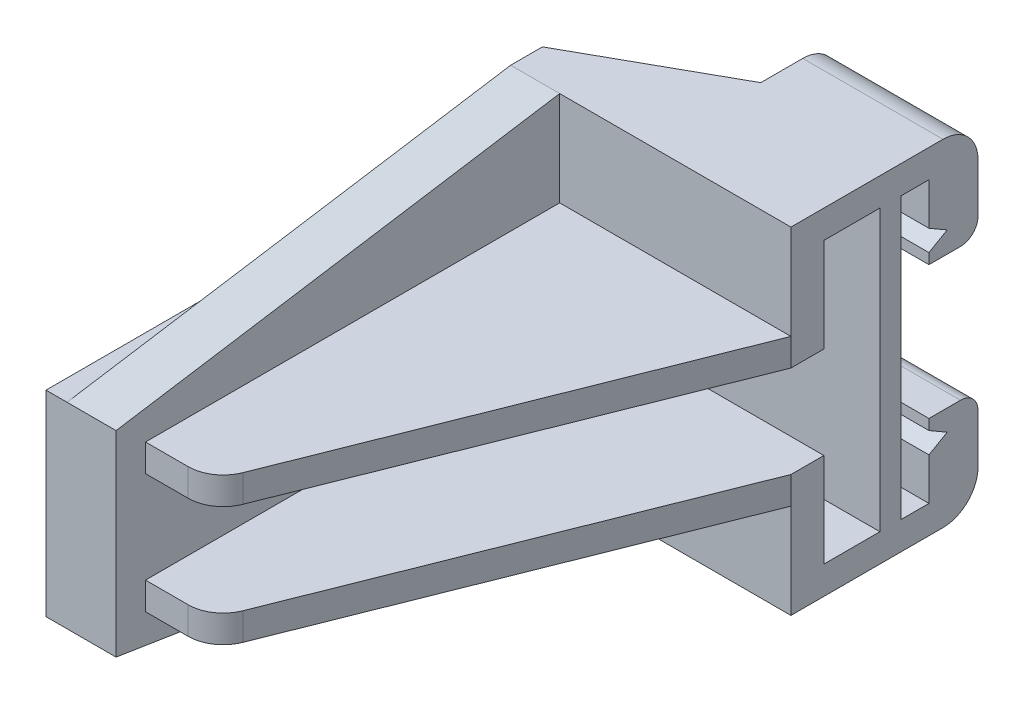
SolidWorks part; units mm, degrees
ref_plane "정면" through (0, 0, 0) normal (0, 0, 1) x (1, 0, 0)
ref_plane "윗면" through (0, 0, 0) normal (0, 1, 0) x (1, 0, 0)
ref_plane "우측면" through (0, 0, 0) normal (1, 0, 0) x (0, 0, -1)
sketch "스케치1" plane through (0, 0, 0) normal (1, 0, 0) x (0, 0, -1)
  line L1 (0, 0) -> (90, 0)
  line L2 (0, 0) -> (0, 48)
  line L3 (0, 48) -> (90, 48)
  line L4 (90, 0) -> (90, 48)
  dimension "D1" = 48
  dimension "D2" = 90
extrude "보스-돌출1" add sketch "스케치1" along normal blind 40
sketch "스케치2" plane through (40, 0, 0) normal (1, 0, 0) x (0, 0, -1)
  line L0 (90, 48) -> (0, 48) construction
  line L1 (79, 44) -> (83, 44)
  line L2 (79, 44) -> (79, 4)
  line L3 (79, 4) -> (83, 4)
  line L4 (83, 44) -> (83, 38)
  line L5 (0, 0) -> (90, 0) construction
  line L6 (90, 0) -> (90, 48) construction
  line L7 (83, 38) -> (85.5981, 36.5)
  line L8 (85.5981, 36.5) -> (83, 35)
  line L9 (-9.108, 24) -> (98.6493, 24) construction
  line L10 (85.5981, 11.5) -> (83, 13)
  line L11 (83, 10) -> (85.5981, 11.5)
  line L12 (83, 35) -> (83, 33.5)
  line L13 (83, 10) -> (83, 4)
  line L14 (83, 14.5) -> (83, 13)
  line L15 (83, 33.5) -> (90, 33.5)
  line L17 (83, 14.5) -> (90, 14.5)
  line L18 (90, 33.5) -> (90, 14.5)
  line L19 (0, 38) -> (63.304, 48)
  line L20 (0, 48) -> (0, 0) construction
  line L21 (63.304, 48) -> (0, 48)
  line L22 (0, 48) -> (0, 38)
  line L23 (0, 10) -> (63.304, 0)
  line L24 (63.304, 0) -> (0, 0)
  line L25 (0, 0) -> (0, 10)
  dimension "D1" = 4
  dimension "D2" = 4
  dimension "D3" = 4
  dimension "D4" = 7
  dimension "D5" = 60
  dimension "D6" = 3
  dimension "D7" = 60
  dimension "D8" = 14.5
  dimension "D9" = 6
  dimension "D10" = 14.5
extrude "컷-돌출1" cut sketch "스케치2" against normal blind 40
sketch "스케치3" plane through (0, 48, 0) normal (0, 1, 0) x (1, 0, 0)
  line L0 (0, 67.8468) -> (20, 79)
  line L1 (0, 90) -> (0, 63.304) construction
  line L2 (20, 79) -> (20, 90)
  line L3 (40, 90) -> (0, 90) construction
  line L4 (20, 90) -> (0, 90)
  line L5 (0, 90) -> (0, 67.8468)
extrude "컷-돌출2" cut sketch "스케치3" against normal through all
sketch "스케치4" plane through (0, 48, 0) normal (0, 1, 0) x (1, 0, 0)
  line L0 (40, 63.304) -> (14.8076, 0)
  line L1 (0, 0) -> (40, 0) construction
  line L2 (14.8076, 0) -> (40, 0)
  line L3 (40, 0) -> (40, 63.304)
extrude "컷-돌출3" cut sketch "스케치4" against normal through all
sketch "스케치5" plane through (40, 0, 0) normal (1, 0, 0) x (0, 0, -1)
  line L0 (-7.1778, 24) -> (95.0444, 24) construction
  line L1 (63.304, 0) -> (63.304, 48) construction
  line L2 (4.2, 34.4889) -> (63.304, 34.4889)
  line L3 (4.2, 34.4889) -> (4.2, 30.5778)
  line L4 (4.2, 30.5778) -> (63.304, 30.5778)
  line L6 (4.2, 17.4222) -> (63.304, 17.4222)
  line L8 (4.2, 13.5111) -> (63.304, 13.5111)
  line L9 (4.2, 13.5111) -> (4.2, 17.4222)
  line L10 (63.304, 34.4889) -> (63.304, 48)
  line L11 (63.304, 48) -> (0, 38)
  line L12 (0, 38) -> (0, 10)
  line L13 (0, 10) -> (63.304, 0)
  line L14 (63.304, 0) -> (63.304, 13.5111)
  line L15 (63.304, 30.5778) -> (63.304, 17.4222)
extrude "컷-돌출4" cut sketch "스케치5" against normal blind 33
sketch "스케치6" plane through (40, 0, 0) normal (1, 0, 0) x (0, 0, -1)
  line L0 (79, 44) -> (79, 4) construction
  line L1 (76, 44) -> (68, 44)
  line L2 (76, 44) -> (76, 4)
  line L3 (76, 4) -> (68, 4)
  line L4 (68, 44) -> (68, 4)
  dimension "D1" = 3
  dimension "D2" = 8
extrude "컷-돌출5" cut sketch "스케치6" against normal through all
sketch "스케치7" plane through (0, 0, -63.304) normal (0, 0, 1) x (1, 0, 0)
  line L0 (7, 30.5778) -> (40, 30.5778) construction
  line L1 (20, 30.5778) -> (40, 30.5778)
  line L2 (20, 30.5778) -> (20, 17.4222)
  line L3 (20, 17.4222) -> (40, 17.4222)
  line L4 (40, 30.5778) -> (40, 17.4222)
extrude "컷-돌출6" cut sketch "스케치7" against normal blind 5
sketch "스케치8" plane through (0, 0, 0) normal (-1, 0, 0) x (0, 0, 1)
  line L1 (0, 38) -> (-28.2, 38)
  line L2 (0, 38) -> (0, 10)
  line L3 (0, 10) -> (-28.2, 10)
  line L4 (-28.2, 38) -> (-28.2, 10)
extrude "보스-돌출2" add sketch "스케치8" along normal blind 3
sketch "스케치9" plane through (0, 0, -79) normal (0, 0, -1) x (-1, 0, 0)
  circle A0 centre (-30, 24) radius 2.25
  dimension "D1" = 4.5
extrude "보스-돌출3" add sketch "스케치9" along normal blind 4
sketch "스케치10" plane through (0, 0, -83) normal (0, 0, -1) x (-1, 0, 0)
  circle A0 centre (-30, 24) radius 1.2
  dimension "D1" = 2.4
extrude "컷-돌출7" cut sketch "스케치10" against normal through all
fillet "필렛1" radius 5 5 edges at (-3, 24, -28.2) (16.479, 15.4667, -4.2) (16.479, 32.5333, -4.2) (30, 0, -90) (30, 48, -90)
fillet "필렛2" radius 2.5 2 edges at (30, 14.5, -90) (30, 33.5, -90)
